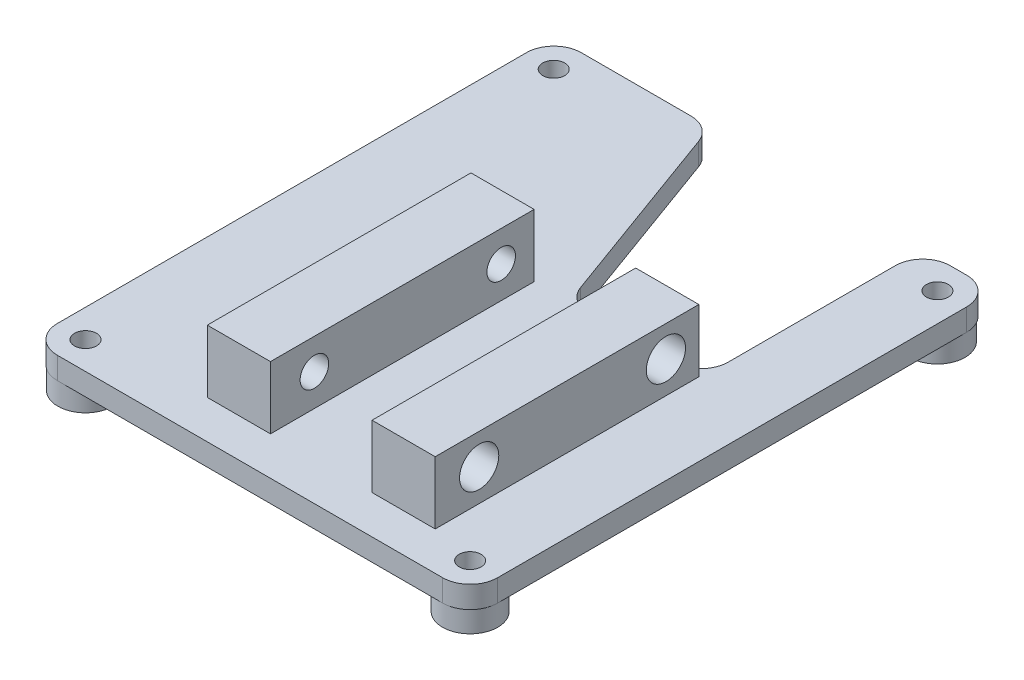
SolidWorks part; units mm, degrees
material "Onyx w/ CF"
ref_plane "Front Plane" through (0, 0, 0) normal (0, 0, 1) x (1, 0, 0)
ref_plane "Top Plane" through (0, 0, 0) normal (0, 1, 0) x (1, 0, 0)
ref_plane "Right Plane" through (0, 0, 0) normal (1, 0, 0) x (0, 0, -1)
sketch "Sketch1" plane through (0, 0, 0) normal (0, 1, 0) x (1, 0, 0)
  line L1 (-10.373, 12) -> (10.373, 12)
  line L2 (-10.373, 12) -> (-10.373, -12)
  line L3 (-10.373, -12) -> (10.373, -12)
  line L4 (10.373, 12) -> (10.373, -12)
  line L5 (-10.373, 12) -> (10.373, -12) construction
  line L6 (-10.373, -12) -> (10.373, 12) construction
  point P0 (0, 0)
  dimension "D1" = 20.746
  dimension "D2" = 24
extrude "Boss-Extrude1" add sketch "Sketch1" along normal blind 5.7
sketch "Sketch9" plane through (0, 0, 0) normal (0, -1, 0) x (1, 0, 0)
  line L0 (-10.373, 12) -> (10.373, 12) construction
  line L1 (4.623, -12) -> (-4.623, -12)
  line L2 (4.623, -12) -> (4.623, 12)
  line L3 (4.623, 12) -> (-4.623, 12)
  line L4 (-4.623, -12) -> (-4.623, 12)
  line L5 (4.623, -12) -> (-4.623, 12) construction
  line L6 (4.623, 12) -> (-4.623, -12) construction
  line L7 (10.373, -12) -> (-10.373, -12) construction
  line L8 (10.373, 12) -> (10.373, -12) construction
  point P0 (0, 0)
  dimension "D1" = 5.75
extrude "Cut-Extrude3" cut sketch "Sketch9" against normal through all
hole_wizard "9/64 (0.14063) Diameter Hole1" positions "Sketch6" profile "Sketch7" hole size "9/64" standard "ANSI Inch"
sketch "Sketch6" plane through (10.373, 0, 0) normal (1, 0, 0) x (0, 0, -1)
  line L4 (9, 2.9) -> (-8, 2.9) construction
  line L7 (-12, 5.7) -> (12, 5.7) construction
  line L9 (-12, 5.7) -> (-12, 0) construction
  line L10 (-8, 2.9) -> (9, 2.9) construction
  point P0 (9, 2.9)
  point P2 (-8, 2.9)
  dimension "D1" = 4
  dimension "D2" = 2.8
  dimension "D3" = 17
sketch "Sketch7" plane through (10.373, 2.9, -9) normal (0, 1, 0) x (0, 0, -1)
  line L0 (0, 0) -> (0, 6.8231)
  line L1 (0, 6.8231) -> (1.786, 5.75)
  line L2 (1.786, 5.75) -> (1.786, 0)
  line L5 (1.786, 0) -> (0, 0)
  line L10 (0, 6.8231) -> (-1.786, 5.75) construction
  line L11 (0, -6.35) -> (0, 107.95) construction
  dimension "Hole Dia." = 3.572
  dimension "Hole Depth" = 5.75
  dimension "Drill Angle" = 118
sketch "Sketch8" plane through (-10.373, 0, 0) normal (-1, 0, 0) x (0, 0, 1)
  line L0 (8, 2.9) -> (-9, 2.9) construction
  line L1 (-12, 5.7) -> (12, 5.7) construction
  line L3 (12, 5.7) -> (12, 0) construction
  circle A0 centre (8, 2.9) radius 1.3
  circle A1 centre (-9, 2.9) radius 1.3
  dimension "D1" = 2.8
  dimension "D4" = 2.6
  dimension "D2" = 17
  dimension "D3" = 4
extrude "Cut-Extrude2" cut sketch "Sketch8" against normal up to surface (5.75 mm away) up to face at (-4.623, 2.85, 0)
sketch "Sketch10" plane through (0, 0, 0) normal (0, -1, 0) x (1, 0, 0)
  line L0 (4.623, 12) -> (10.373, 12) construction
  line L1 (17.053, 15.5) -> (-23.027, 15.5)
  line L2 (17.053, 15.5) -> (17.053, -32.2)
  line L3 (17.053, -32.2) -> (-23.027, -32.2)
  line L4 (-23.027, 15.5) -> (-23.027, -32.2)
  line L5 (10.373, 12) -> (10.373, -12) construction
  dimension "D1" = 40.08
  dimension "D2" = 47.7
  dimension "D3" = 3.5
  dimension "D4" = 6.68
extrude "Boss-Extrude2" add sketch "Sketch10" along normal blind 2
sketch "Sketch11" plane through (0, -2, 0) normal (0, -1, 0) x (1, 0, 0)
  line L0 (-23.027, 15.5) -> (-23.027, -32.2) construction
  line L1 (17.053, 15.5) -> (-23.027, 15.5) construction
  line L2 (17.053, -32.2) -> (17.053, 15.5) construction
  line L3 (-23.027, -32.2) -> (17.053, -32.2) construction
  circle A0 centre (14.453, 12.9) radius 2.515
  circle A1 centre (-20.475, 12.985) radius 2.515
  circle A2 centre (14.45, -29.6362) radius 2.515
  circle A3 centre (-20.475, -29.6362) radius 2.515
  dimension "D1" = 2.6
  dimension "D2" = 2.6
  dimension "D3" = 2.552
  dimension "D4" = 2.5638
  dimension "D5" = 2.603
  dimension "D6" = 2.5638
  dimension "D7" = 2.552
  dimension "D8" = 2.515
extrude "Boss-Extrude3" add sketch "Sketch11" along normal blind 2
sketch "Sketch12" plane through (0, -4, 0) normal (0, -1, 0) x (1, 0, 0)
  circle A0 centre (14.453, 12.9) radius 1
  circle A1 centre (-20.475, 12.985) radius 1
  circle A2 centre (-20.475, -29.6362) radius 1
  circle A3 centre (14.45, -29.6362) radius 1
  circle A4 centre (-20.475, -29.6362) radius 2.515 construction
  circle A5 centre (14.45, -29.6362) radius 2.515 construction
  circle A6 centre (14.453, 12.9) radius 2.515 construction
  circle A7 centre (-20.475, 12.985) radius 2.515 construction
  dimension "D1" = 2
extrude "Cut-Extrude4" cut sketch "Sketch12" against normal through all
fillet "Fillet2" radius 2.5 4 edges at (17.053, -1, -32.2) (-23.027, -1, -32.2) (-23.027, -1, 15.5) (17.053, -1, 15.5)
sketch "Sketch14" plane through (0, 0, 0) normal (0, 1, 0) x (1, 0, 0)
  line L4 (10.553, 32.2) -> (10.553, 12)
  line L5 (10.553, 12) -> (-1.447, 12)
  line L6 (-1.447, 12) -> (-8.7992, 32.2)
  line L7 (-20.527, 32.2) -> (14.553, 32.2) construction
  line L8 (10.373, 12) -> (4.623, 12) construction
  line L9 (-8.7992, 32.2) -> (10.553, 32.2)
  dimension "D1" = 4
  dimension "D2" = 12
  dimension "D3" = 20
extrude "Cut-Extrude5" cut sketch "Sketch14" against normal through all
fillet "Fillet3" radius 2.5 4 edges at (10.553, -1, -12) (-1.447, -1, -12) (10.553, -1, -32.2) (-8.7992, -1, -32.2)
sketch "Sketch15" plane through (0, 5.7, 0) normal (0, 1, 0) x (1, 0, 0)
  line L0 (8.053, 12) -> (10.373, 12)
  line L1 (8.053, 12) -> (4.623, 12) construction
  line L2 (10.373, -12) -> (10.373, 13.5685) construction
  line L3 (10.373, 12) -> (10.373, 13.5685)
  arc A0 (8.053, 12) -> (10.373, 13.5685) centre (8.053, 14.5) ccw construction
  arc A1 (10.373, 13.5685) -> (8.053, 12) centre (8.053, 14.5) cw
extrude "Cut-Extrude6" cut sketch "Sketch15" against normal up to surface (5.7 mm away) up to face at (1.0152, 0, -12.2988)
